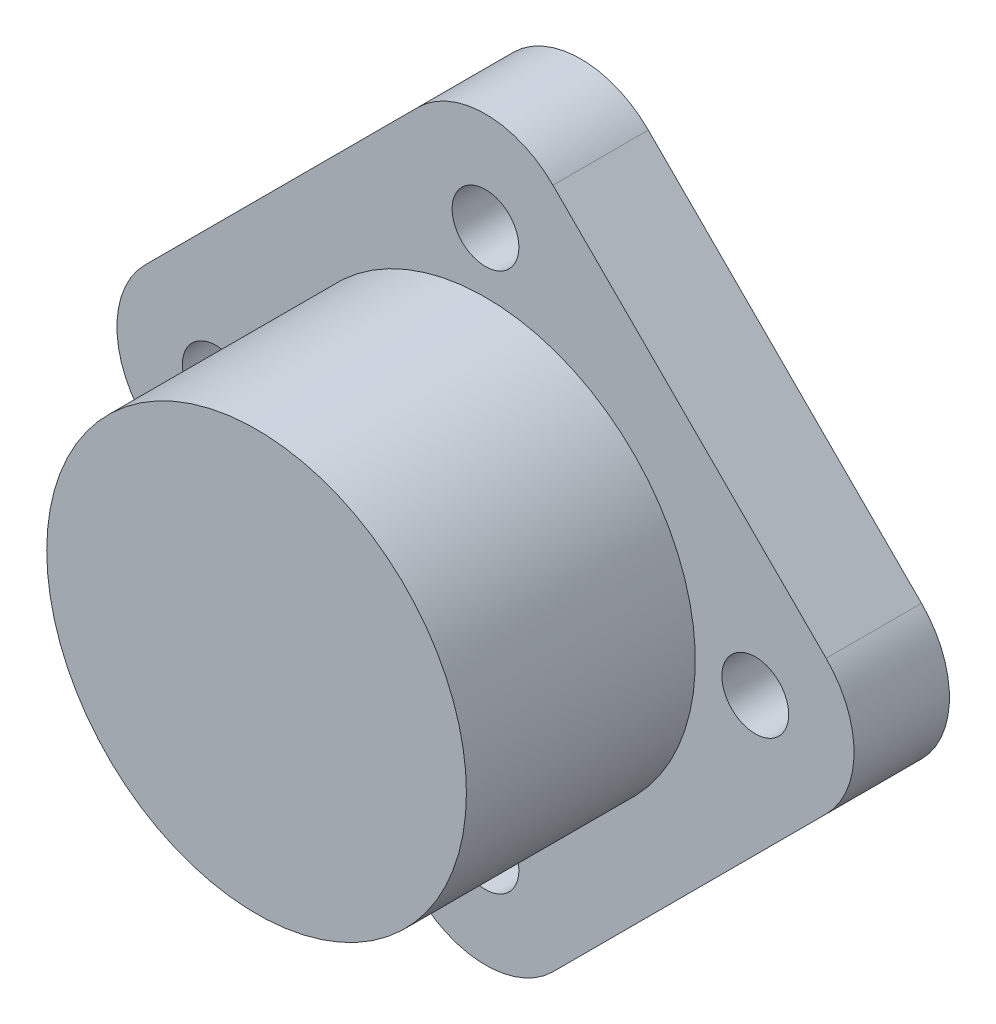
SolidWorks part; units mm, degrees
ref_plane "Front Plane" through (0, 0, 0) normal (0, 0, 1) x (1, 0, 0)
ref_plane "Top Plane" through (0, 0, 0) normal (0, 1, 0) x (1, 0, 0)
ref_plane "Right Plane" through (0, 0, 0) normal (1, 0, 0) x (0, 0, -1)
sketch "Sketch1" plane through (0, 0, 0) normal (0, 0, 1) x (1, 0, 0)
  line L0 (10.6961, -43.2693) -> (-25.2249, -7.3483)
  line L1 (-25.2249, 11.0628) -> (10.6961, 46.9838)
  line L2 (29.1072, 46.9838) -> (65.0282, 11.0628)
  line L3 (29.1072, -43.2693) -> (65.0282, -7.3483)
  line L4 (-25.2249, -7.3483) -> (-34.4304, 1.8572)
  line L5 (-34.4304, 1.8572) -> (-25.2249, 11.0628)
  line L6 (10.6961, 46.9838) -> (19.9017, 56.1893)
  line L7 (19.9017, 56.1893) -> (29.1072, 46.9838)
  line L8 (65.0282, 11.0628) -> (74.2338, 1.8572)
  line L9 (74.2338, 1.8572) -> (65.0282, -7.3483)
  line L10 (10.6961, -43.2693) -> (19.9017, -52.4749)
  line L11 (19.9017, -52.4749) -> (29.1072, -43.2693)
  line L12 (-7.2644, 29.0233) -> (47.0677, -25.3088) construction
  line L13 (46.3766, 29.7144) -> (-7.9555, -24.6177) construction
  circle A4 centre (-16.0194, 1.8572) radius 4.445
  circle A5 centre (19.9017, 37.7782) radius 4.445
  circle A6 centre (19.9017, -34.0638) radius 4.445
  circle A7 centre (55.8227, 1.8572) radius 4.445
  point P3 (-7.2644, -25.3088)
  dimension "D2" = 50.8
  dimension "D1" = 50.8
extrude "Boss-Extrude1" add sketch "Sketch1" along normal blind 12.7
fillet "Fillet1" radius 12.7 4 edges at (19.9017, -52.4749, 6.35) (74.2338, 1.8572, 6.35) (-34.4304, 1.8572, 6.35) (19.9017, 56.1893, 6.35)
sketch "Sketch2" plane through (0, 0, 0) normal (0, 0, 1) x (1, 0, 0)
  line L0 (19.9017, 50.9288) -> (19.9017, -47.2144) construction
  arc A0 (28.8819, 47.2091) -> (10.9214, 47.2091) centre (19.9017, 38.2288) ccw construction
  arc A1 (10.9214, -43.4946) -> (28.8819, -43.4946) centre (19.9017, -34.5144) ccw construction
  circle A2 centre (19.9017, 1.8572) radius 27.94
extrude "Boss-Extrude2" add sketch "Sketch2" along normal blind 43.18
